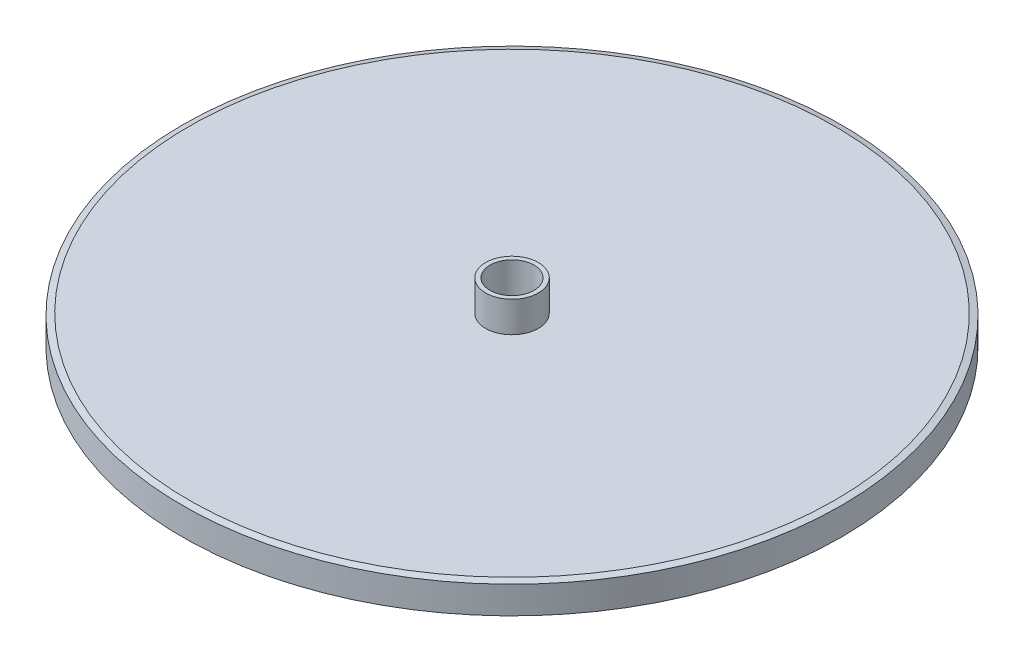
SolidWorks part; units mm, degrees
material "Сталь ШХ15 ГОСТ 801-78"
ref_plane "Plane1" through (0, 0, 0) normal (0, 0, 1) x (1, 0, 0)
ref_plane "Plane2" through (0, 0, 0) normal (0, 1, 0) x (1, 0, 0)
ref_plane "Plane3" through (0, 0, 0) normal (1, 0, 0) x (0, 0, -1)
sketch "Эскиз1" plane through (0, 0, 0) normal (0, 0, 1) x (1, 0, 0)
  line L0 (0, 0) -> (37.5, 0)
  line L1 (37.5, 0) -> (37.5, 3.5)
  line L2 (37.5, 3.5) -> (3, 3.5)
  line L3 (3, 3.5) -> (3, 7)
  line L4 (3, 7) -> (0, 7)
  line L5 (0, 7) -> (0, 0)
  dimension "D1" = 3.5
  dimension "30" = 37.5
  dimension "D3" = 3
  dimension "D4" = 3.5
ref_axis "Ось1" through (0, 7, 0) along (0, -1, 0)
revolve "Повернуть2" add sketch "Эскиз1" angle 360 about axis through (0, 7, 0) along (0, -1, 0)
chamfer "Фаска1" distance 0.705 angle 15 1 edges at (-37.5, 3.5, 0) first distance on face at (-3, 3.5, 0)
sketch "Эскиз2" plane through (0, 0, 0) normal (0, -1, 0) x (-1, 0, 0)
  circle A0 centre (0, 0) radius 2.5
extrude "Вырез-Вытянуть3" cut sketch "Эскиз2" against normal through all both
chamfer "Фаска2" distance 0.705 angle 15 1 edges at (-37.5, 0, 0) first distance on face at (0, 0, -2.5)
